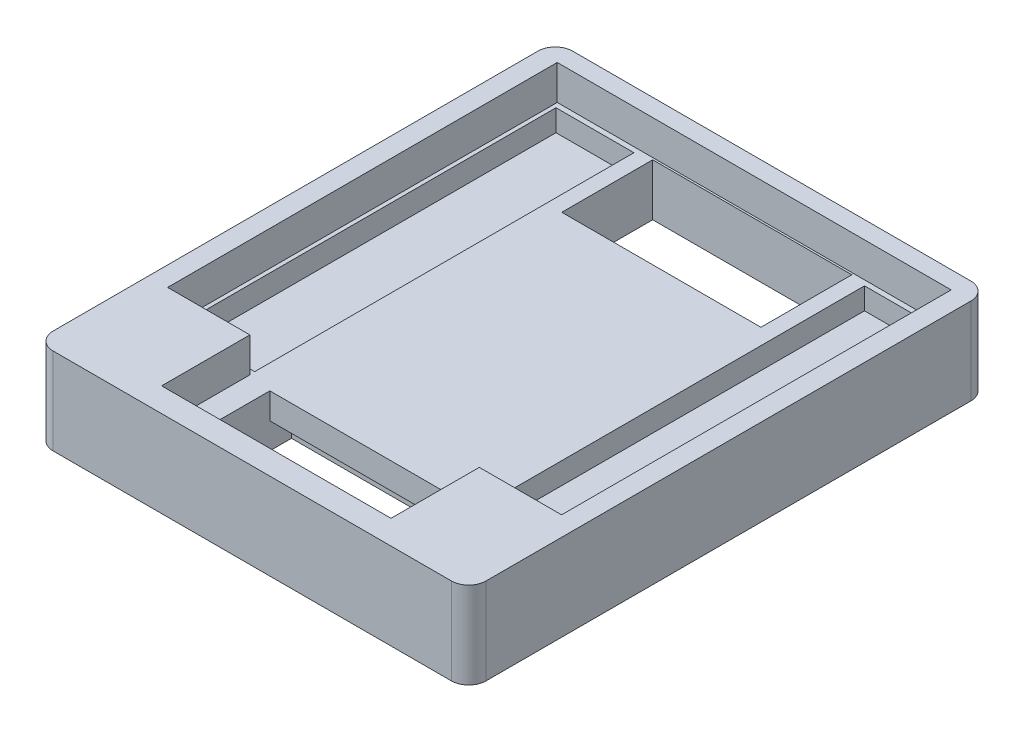
SolidWorks part; units mm, degrees
ref_plane "Front Plane" through (0, 0, 0) normal (0, 0, 1) x (1, 0, 0)
ref_plane "Top Plane" through (0, 0, 0) normal (0, 1, 0) x (1, 0, 0)
ref_plane "Right Plane" through (0, 0, 0) normal (1, 0, 0) x (0, 0, -1)
sketch "Sketch1" plane through (0, 0, 0) normal (0, 1, 0) x (1, 0, 0)
  line L1 (-25, 30) -> (25, 30)
  line L2 (-25, 30) -> (-25, -30)
  line L3 (-25, -30) -> (25, -30)
  line L4 (25, 30) -> (25, -30)
  line L5 (-25, 30) -> (25, -30) construction
  line L6 (-25, -30) -> (25, 30) construction
  point P0 (0, 0)
  dimension "D1" = 60
  dimension "D2" = 50
extrude "Boss-Extrude1" add sketch "Sketch1" along normal blind 10
sketch "Sketch2" plane through (0, 10, 0) normal (0, 1, 0) x (1, 0, 0)
  line L0 (-13.25, -22.1225) -> (-12.75, -22.1225) construction
  line L1 (-22.75, 27.975) -> (22.75, 27.975)
  line L2 (-22.75, 27.975) -> (-22.75, -17.025)
  line L3 (-22.75, -17.025) -> (-13.25, -17.025)
  line L4 (22.75, 27.975) -> (22.75, -17.025)
  line L5 (-22.75, 27.975) -> (22.75, -17.025) construction
  line L6 (-22.75, -17.025) -> (22.75, 27.975) construction
  line L7 (13.25, -17.025) -> (22.75, -17.025)
  line L8 (-13.25, -17.025) -> (-13.25, -27.22)
  line L9 (-13.25, -27.22) -> (13.25, -27.22)
  line L10 (13.25, -17.025) -> (13.25, -27.22)
  line L11 (-12.75, -16.72) -> (-12.75, -26.72) construction
  line L12 (-12.75, -22.1225) -> (12.75, -22.1225) construction
  line L13 (12.75, -26.72) -> (12.75, -16.72) construction
  line L14 (12.75, -22.1225) -> (13.25, -22.1225) construction
  line L15 (0, -26.72) -> (0, -27.22) construction
  line L16 (-12.75, -26.72) -> (12.75, -26.72) construction
  point P0 (0, 5.475)
  dimension "D1" = 45
  dimension "D2" = 45.5
  dimension "D3" = 0.5
  dimension "D4" = 0.5
extrude "Cut-Extrude1" cut sketch "Sketch2" against normal blind 4
sketch "Sketch3" plane through (0, 0, 0) normal (0, -1, 0) x (1, 0, 0)
  line L0 (10.5, -27) -> (-10.5, -18) construction
  line L1 (-10.5, -18) -> (0, -22.5) construction
  line L2 (0, 30) -> (0, 21.72) construction
  line L3 (11.5, -27.75) -> (-11.5, -27.75)
  line L4 (11.5, -27.75) -> (11.5, -17.25)
  line L5 (11.5, -17.25) -> (-11.5, -17.25)
  line L6 (-11.5, -27.75) -> (-11.5, -17.25)
  line L7 (11.5, -27.75) -> (-11.5, -17.25) construction
  line L8 (11.5, -17.25) -> (-11.5, -27.75) construction
  line L9 (-25, 30) -> (25, 30) construction
  line L11 (10.5, 17.47) -> (-10.5, 17.47)
  line L12 (10.5, 17.47) -> (10.5, 25.97)
  line L13 (10.5, 25.97) -> (-10.5, 25.97)
  line L14 (-10.5, 17.47) -> (-10.5, 25.97)
  line L15 (10.5, 17.47) -> (-10.5, 25.97) construction
  line L16 (10.5, 25.97) -> (-10.5, 17.47) construction
  dimension "D1" = 23
  dimension "D2" = 10.5
  dimension "D3" = 8.5
extrude "Cut-Extrude2" cut sketch "Sketch3" against normal blind 10
sketch "Sketch4" plane through (0, 6, 0) normal (0, 1, 0) x (1, 0, 0)
  line L0 (-13.7721, 27) -> (-21.815, -16.05) construction
  line L1 (21.815, 27) -> (-21.815, 27) construction
  line L2 (-21.815, -16.05) -> (-17.7936, 5.475) construction
  line L3 (13.8625, 27) -> (21.815, -16.05) construction
  line L4 (-21.815, -16.05) -> (21.815, -16.05) construction
  line L5 (21.815, -16.05) -> (21.815, 27) construction
  line L6 (21.815, -16.05) -> (17.8387, 5.475) construction
  line L8 (-22.2936, 27.375) -> (-13.2936, 27.375)
  line L9 (-22.2936, 27.375) -> (-22.2936, -16.425)
  line L10 (-22.2936, -16.425) -> (-13.2936, -16.425)
  line L11 (-13.2936, 27.375) -> (-13.2936, -16.425)
  line L12 (-22.2936, 27.375) -> (-13.2936, -16.425) construction
  line L13 (-22.2936, -16.425) -> (-13.2936, 27.375) construction
  line L14 (22.3387, 27.375) -> (13.3387, 27.375)
  line L15 (22.3387, 27.375) -> (22.3387, -16.425)
  line L16 (22.3387, -16.425) -> (13.3387, -16.425)
  line L17 (13.3387, 27.375) -> (13.3387, -16.425)
  line L18 (22.3387, 27.375) -> (13.3387, -16.425) construction
  line L19 (22.3387, -16.425) -> (13.3387, 27.375) construction
  dimension "D1" = 43.8
  dimension "D2" = 9
extrude "Cut-Extrude3" cut sketch "Sketch4" against normal blind 2.5
sketch "Sketch5" plane through (0, 0, 0) normal (0, -1, 0) x (1, 0, 0)
  line L1 (17.5, -15.5) -> (-17.5, -15.5)
  line L2 (17.5, -15.5) -> (17.5, 3.5)
  line L3 (17.5, 3.5) -> (-17.5, 3.5)
  line L4 (-17.5, -15.5) -> (-17.5, 3.5)
  line L5 (17.5, -15.5) -> (-17.5, 3.5) construction
  line L6 (17.5, 3.5) -> (-17.5, -15.5) construction
  point P0 (0, -6)
  dimension "D1" = 19
  dimension "D2" = 35
extrude "Cut-Extrude4" cut sketch "Sketch5" against normal blind 1.5
sketch "Sketch6" plane through (0, 0, 0) normal (0, -1, 0) x (1, 0, 0)
  line L1 (6.15, 6.6) -> (-6.15, 6.6)
  line L2 (6.15, 6.6) -> (6.15, 13.4)
  line L3 (6.15, 13.4) -> (-6.15, 13.4)
  line L4 (-6.15, 6.6) -> (-6.15, 13.4)
  line L5 (6.15, 6.6) -> (-6.15, 13.4) construction
  line L6 (6.15, 13.4) -> (-6.15, 6.6) construction
  point P0 (0, 10)
  dimension "D1" = 6.8
  dimension "D2" = 12.3
extrude "Cut-Extrude5" cut sketch "Sketch6" against normal blind 1.5
fillet "Fillet1" radius 2 4 edges at (-25, 5, -30) (-25, 5, 30) (25, 5, 30) (25, 5, -30)
sketch "Sketch7" plane through (0, 0, 0) normal (0, -1, 0) x (1, 0, 0)
  line L1 (10.5, 17.47) -> (-10.5, 17.47)
  line L2 (10.5, 17.47) -> (10.5, 14.97)
  line L3 (10.5, 14.97) -> (-10.5, 14.97)
  line L4 (-10.5, 17.47) -> (-10.5, 14.97)
  dimension "D1" = 2.5
extrude "Cut-Extrude6" cut sketch "Sketch7" against normal blind 3
